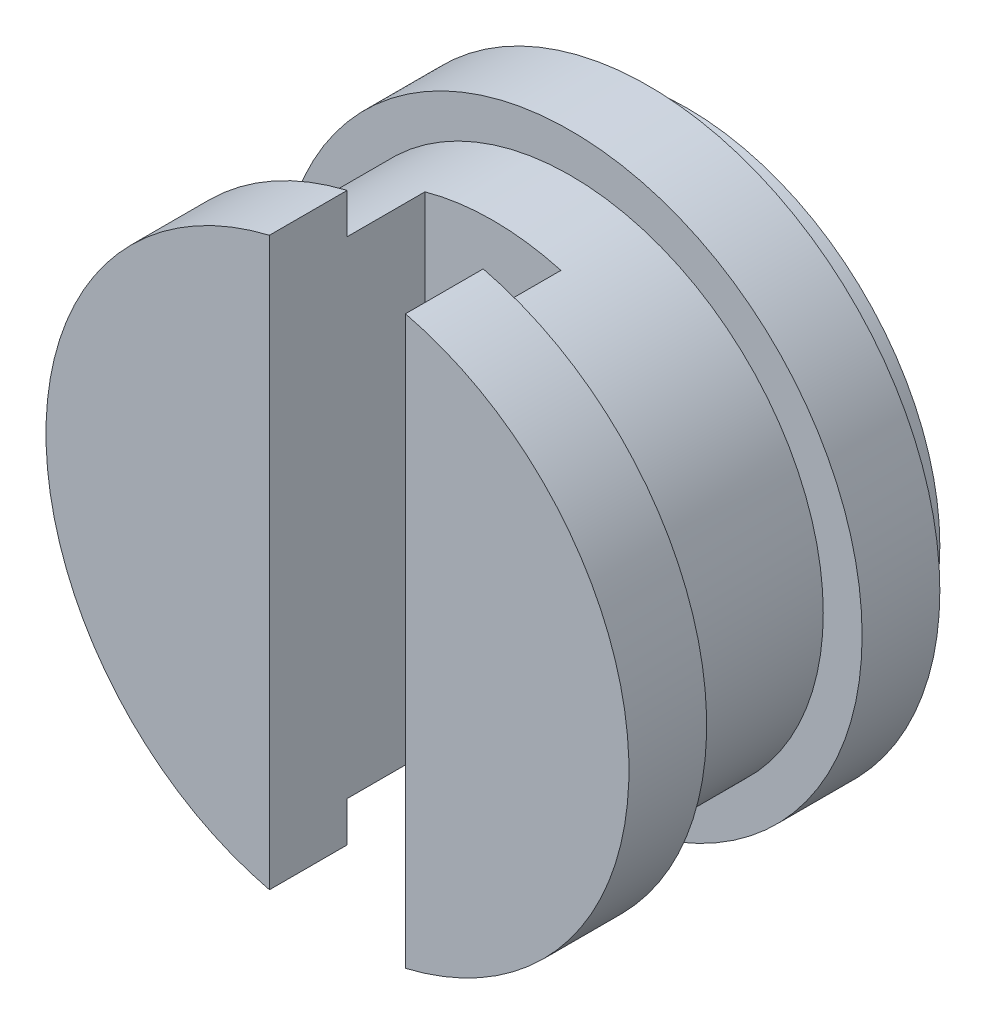
SolidWorks part; units mm, degrees
ref_plane "Спереди" through (0, 0, 0) normal (0, 0, 1) x (1, 0, 0)
ref_plane "Сверху" through (0, 0, 0) normal (0, 1, 0) x (1, 0, 0)
ref_plane "Справа" through (0, 0, 0) normal (1, 0, 0) x (0, 0, -1)
sketch "Эскиз1" plane through (0, 0, 0) normal (0, 0, 1) x (1, 0, 0)
  circle A0 centre (0, 0) radius 13
  dimension "D1" = 26
extrude "Бобышка-Вытянуть1" add sketch "Эскиз1" along normal blind 16
sketch "Эскиз2" plane through (0, 0, 0) normal (0, 0, 1) x (1, 0, 0)
  circle A0 centre (0, 0) radius 15
  dimension "D1" = 30
extrude "Бобышка-Вытянуть2" add sketch "Эскиз2" along normal blind 4 from offset 2
sketch "Эскиз3" plane through (0, 0, 0) normal (0, 0, 1) x (1, 0, 0)
  line L1 (-7.5, -2.5) -> (7.5, -2.5)
  line L2 (-7.5, -2.5) -> (-7.5, 2.5)
  line L3 (-7.5, 2.5) -> (7.5, 2.5)
  line L4 (7.5, -2.5) -> (7.5, 2.5)
  line L5 (-7.5, -2.5) -> (7.5, 2.5) construction
  line L6 (-7.5, 2.5) -> (7.5, -2.5) construction
  point P0 (0, 0)
  dimension "D1" = 5
  dimension "D2" = 15
extrude "Вырез-Вытянуть1" cut sketch "Эскиз3" along normal blind 8
sketch "Эскиз4" plane through (0, 0, 0) normal (0, 0, 1) x (1, 0, 0)
  circle A0 centre (0, 0) radius 11
  dimension "D1" = 22
extrude "Вырез-Вытянуть2" cut sketch "Эскиз4" along normal blind 6
sketch "Эскиз5" plane through (0, 0, 0) normal (0, 0, 1) x (1, 0, 0)
  circle A0 centre (0, 0) radius 15
  dimension "D1" = 30
extrude "Бобышка-Вытянуть3" add sketch "Эскиз5" along normal blind 4 from offset 14
sketch "Эскиз6" plane through (0, 0, 0) normal (0, 0, 1) x (1, 0, 0)
  line L1 (-3.5, -16) -> (3.5, -16)
  line L2 (-3.5, -16) -> (-3.5, 16)
  line L3 (-3.5, 16) -> (3.5, 16)
  line L4 (3.5, -16) -> (3.5, 16)
  line L5 (-3.5, -16) -> (3.5, 16) construction
  line L6 (-3.5, 16) -> (3.5, -16) construction
  point P0 (0, 0)
  dimension "D1" = 32
  dimension "D2" = 7
extrude "Вырез-Вытянуть3" cut sketch "Эскиз6" along normal blind 8 from offset 10
